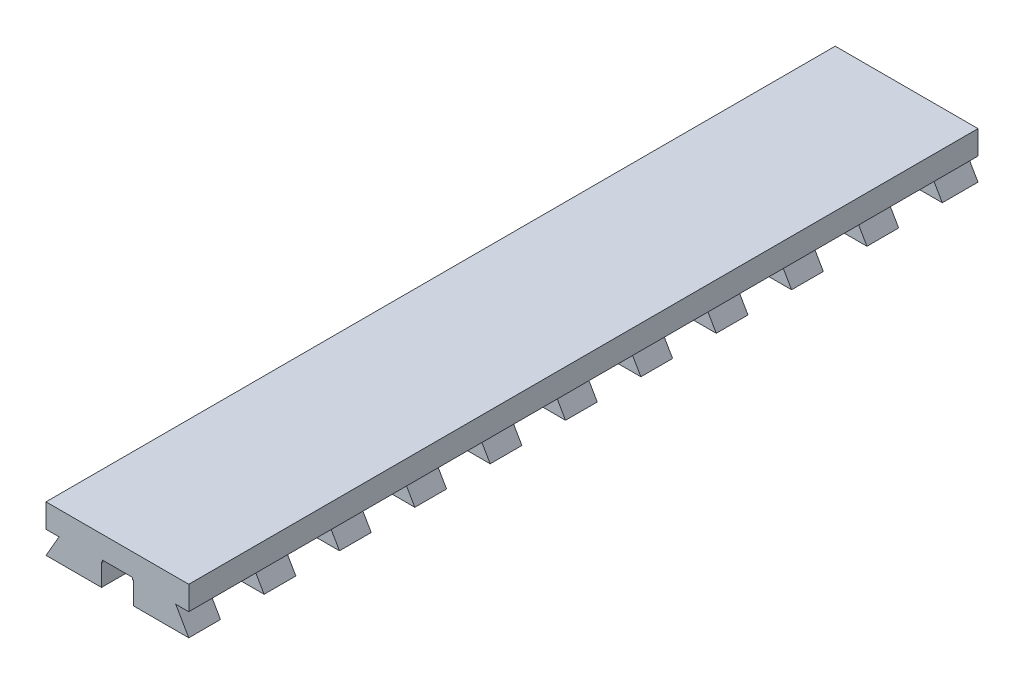
SolidWorks part; units mm, degrees
material "6061-T4 (SS)"
ref_plane "Front Plane" through (0, 0, 0) normal (0, 0, 1) x (1, 0, 0)
ref_plane "Top Plane" through (0, 0, 0) normal (0, 1, 0) x (1, 0, 0)
ref_plane "Right Plane" through (0, 0, 0) normal (1, 0, 0) x (0, 0, -1)
sketch "Sketch1" plane through (0, 0, 0) normal (0, 0, 1) x (1, 0, 0)
  line L0 (-9, 0) -> (9, 0)
  line L1 (9, 0) -> (9, -3)
  line L2 (9, -3) -> (7.3546, -3)
  line L3 (7.3546, -3) -> (9, -5.85)
  line L4 (9, -5.85) -> (2, -5.85)
  line L5 (2, -5.85) -> (2, -3.0524)
  line L7 (-2, -3.0524) -> (-2, -5.85)
  line L8 (-2, -5.85) -> (-9, -5.85)
  line L9 (-9, -5.85) -> (-7.3546, -3)
  line L10 (-7.3546, -3) -> (-9, -3)
  line L11 (-9, -3) -> (-9, 0)
  line L12 (-1.9, -2.8) -> (1.9, -2.8)
  line L13 (1.9, -2.8) -> (1.9, -3.0524)
  line L14 (1.9, -3.0524) -> (2, -3.0524)
  line L15 (-2, -3.0524) -> (-1.9, -3.0524)
  line L16 (-1.9, -3.0524) -> (-1.9, -2.8)
  point P14 (0, -2.8)
  dimension "D1" = 18
  dimension "D2" = 3
  dimension "D3" = 3.05
  dimension "D4" = 3.8
  dimension "D5" = 60
  dimension "D6" = 5.85
  dimension "D8" = 7
extrude "Boss-Extrude1" add sketch "Sketch1" along normal mid plane 99.5
sketch "Sketch2" plane through (9, 0, 0) normal (1, 0, 0) x (0, 0, -1)
  line L0 (-49.75, -3) -> (49.75, -3) construction
  line L1 (-45.75, -3) -> (-40.25, -3)
  line L2 (-45.75, -3) -> (-45.75, -8.5)
  line L3 (-45.75, -8.5) -> (-40.25, -8.5)
  line L4 (-40.25, -3) -> (-40.25, -8.5)
  line L5 (-45.75, -3) -> (-40.25, -8.5) construction
  line L6 (-45.75, -8.5) -> (-40.25, -3) construction
  line L7 (-49.75, -3) -> (-49.75, 0) construction
  line L8 (-36.25, -3) -> (-36.25, -8.5)
  line L9 (-36.25, -3) -> (-30.75, -3)
  line L10 (-30.75, -3) -> (-30.75, -8.5)
  line L11 (-36.25, -8.5) -> (-30.75, -8.5)
  line L12 (-36.25, -3) -> (-30.75, -8.5) construction
  line L13 (-36.25, -8.5) -> (-30.75, -3) construction
  line L14 (-26.75, -3) -> (-26.75, -8.5)
  line L15 (-26.75, -3) -> (-21.25, -3)
  line L16 (-21.25, -3) -> (-21.25, -8.5)
  line L17 (-26.75, -8.5) -> (-21.25, -8.5)
  line L18 (-26.75, -3) -> (-21.25, -8.5) construction
  line L19 (-26.75, -8.5) -> (-21.25, -3) construction
  line L20 (-17.25, -3) -> (-17.25, -8.5)
  line L21 (-17.25, -3) -> (-11.75, -3)
  line L22 (-11.75, -3) -> (-11.75, -8.5)
  line L23 (-17.25, -8.5) -> (-11.75, -8.5)
  line L24 (-17.25, -3) -> (-11.75, -8.5) construction
  line L25 (-17.25, -8.5) -> (-11.75, -3) construction
  line L26 (-7.75, -3) -> (-7.75, -8.5)
  line L27 (-7.75, -3) -> (-2.25, -3)
  line L28 (-2.25, -3) -> (-2.25, -8.5)
  line L29 (-7.75, -8.5) -> (-2.25, -8.5)
  line L30 (-7.75, -3) -> (-2.25, -8.5) construction
  line L31 (-7.75, -8.5) -> (-2.25, -3) construction
  line L32 (1.75, -3) -> (1.75, -8.5)
  line L33 (1.75, -3) -> (7.25, -3)
  line L34 (7.25, -3) -> (7.25, -8.5)
  line L35 (1.75, -8.5) -> (7.25, -8.5)
  line L36 (1.75, -3) -> (7.25, -8.5) construction
  line L37 (1.75, -8.5) -> (7.25, -3) construction
  line L38 (11.25, -3) -> (11.25, -8.5)
  line L39 (11.25, -3) -> (16.75, -3)
  line L40 (16.75, -3) -> (16.75, -8.5)
  line L41 (11.25, -8.5) -> (16.75, -8.5)
  line L42 (11.25, -3) -> (16.75, -8.5) construction
  line L43 (11.25, -8.5) -> (16.75, -3) construction
  line L44 (20.75, -3) -> (20.75, -8.5)
  line L45 (20.75, -3) -> (26.25, -3)
  line L46 (26.25, -3) -> (26.25, -8.5)
  line L47 (20.75, -8.5) -> (26.25, -8.5)
  line L48 (20.75, -3) -> (26.25, -8.5) construction
  line L49 (20.75, -8.5) -> (26.25, -3) construction
  line L50 (30.25, -3) -> (30.25, -8.5)
  line L51 (30.25, -3) -> (35.75, -3)
  line L52 (35.75, -3) -> (35.75, -8.5)
  line L53 (30.25, -8.5) -> (35.75, -8.5)
  line L54 (30.25, -3) -> (35.75, -8.5) construction
  line L55 (30.25, -8.5) -> (35.75, -3) construction
  line L56 (39.75, -3) -> (39.75, -8.5)
  line L57 (39.75, -3) -> (45.25, -3)
  line L58 (45.25, -3) -> (45.25, -8.5)
  line L59 (39.75, -8.5) -> (45.25, -8.5)
  line L60 (39.75, -3) -> (45.25, -8.5) construction
  line L61 (39.75, -8.5) -> (45.25, -3) construction
  point P4 (-43, -5.75)
  point P15 (-33.5, -5.75)
  point P20 (-24, -5.75)
  point P25 (-14.5, -5.75)
  point P30 (-5, -5.75)
  point P35 (4.5, -5.75)
  point P40 (14, -5.75)
  point P45 (23.5, -5.75)
  point P50 (33, -5.75)
  point P55 (42.5, -5.75)
  dimension "D1" = 5.5
  dimension "D2" = 5.5
  dimension "D3" = 4
extrude "Cut-Extrude1" cut sketch "Sketch2" against normal through all and the other way through all
